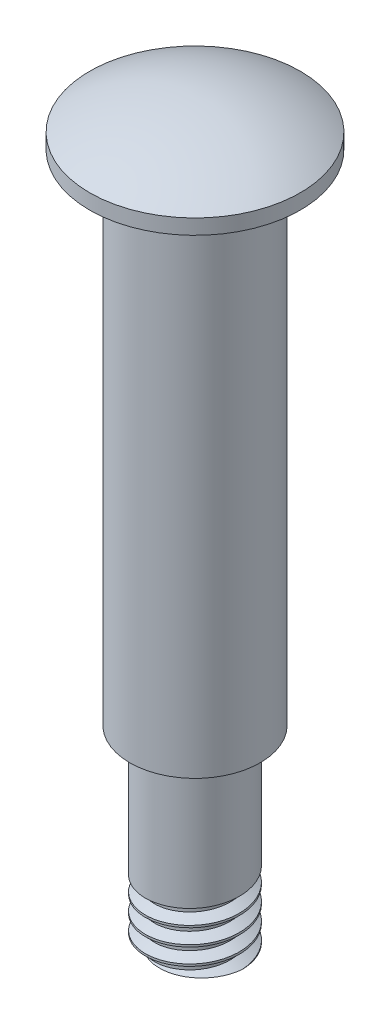
SolidWorks part; units mm, degrees
material "6061-T6 (SS)"
ref_plane "Front Plane" through (0, 0, 0) normal (1, 0, 0) x (0, 1, 0)
ref_plane "Top Plane" through (0, 0, 0) normal (0, 0, 1) x (0, 1, 0)
ref_plane "Right Plane" through (0, 0, 0) normal (0, 1, 0) x (-1, 0, 0)
sketch "Sketch1" plane through (0, 0, 0) normal (1, 0, 0) x (0, 1, 0)
  line L0 (0, 0) -> (-57.9625, 0)
  line L1 (-57.9625, 0) -> (-57.9625, 3.9688)
  line L2 (-57.9625, 3.9688) -> (-42.0875, 3.9688)
  line L3 (-42.0875, 3.9688) -> (-42.0875, 5.5)
  line L4 (-42.0875, 5.5) -> (0, 5.5)
  line L5 (0, 5.5) -> (0, 8.89)
  line L6 (0, 8.89) -> (3.81, 8.89)
  line L7 (3.81, 8.89) -> (3.81, 0)
  line L8 (3.81, 0) -> (0, 0)
  line L9 (-57.9625, -3.9687) -> (-57.9625, 3.9688)
  line L11 (-57.9625, 0) -> (-57.9625, 3.9688) construction
  line L13 (-42.0875, -5.5) -> (-42.0875, 5.5)
  arc A0 (3.81, 0) -> (1.27, 8.89) centre (-13.0175, 0) ccw
  point P15 (-57.9625, 0)
  point P17 (-42.0875, 0)
  dimension "D3" = 8.89
  dimension "D4" = 3.81
  dimension "D5" = 15.875
  dimension "D6" = 90
  dimension "D7" = 42.0875
  dimension "D8" = 3.39
  dimension "D9" = 0
  dimension "D10" = 1.27
  dimension "D2" = 7.9375
  dimension "D11" = 11
revolve "Revolve1" add sketch "Sketch1" angle 360 about L0 region at (0, -18.7121, 2.8609) region at (0, -50.025, 1.9844)
thread "Thread1" pitch 1.4111 method cut profile "Thread Profile2" start angle 0, offset 1.4111, length 6.35, pitch 1.4111, diameter 7.9375
ref_plane "Plane2" through (3.9688, -59.3736, 0) normal (0, 0, 1) x (1, 0, 0)
sketch "Thread Profile2" plane through (3.9688, -59.3736, 0) normal (0, 0, 1) x (1, 0, 0)
  line L0 (0, 0) -> (0, 1.4111) construction
  line L11 (0, 0) -> (0, 1.2347)
  line L12 (0, 1.2347) -> (-0.7638, 0.7937)
  line L13 (-0.7638, 0.7937) -> (-0.7638, 0.441)
  line L15 (-0.7638, 0.441) -> (0, 0)
  line L17 (-0.7638, 0.6174) -> (0, 0.6174) construction
  point P2 (0, 0)
  dimension "Pitch" = 1.4111
  dimension "Profile_Angle" = 60
  dimension "Profile_Land" = 0.3528
  dimension "Profile_Height" = 0.7638
equation "\"D11@Sketch1\"=11mm"
equation "\"nut\"= 0.15"
equation "\"washer\"= 0.0625"
equation "\"wall\"= 0.35"
equation "\"pin support\"= 32.5mm"
equation "\"wall support\" = 0.125"
equation "\"D5@Sketch1\"=\"nut\"+\"washer\"*2+\"wall\""
equation "\"D7@Sketch1\"= \"pin support\" + \"wall support\" - \"washer\" + \"gear\" + \"clearance\""
equation "\"gear\"= 6mm"
equation "\"clearance\"= 2mm"
